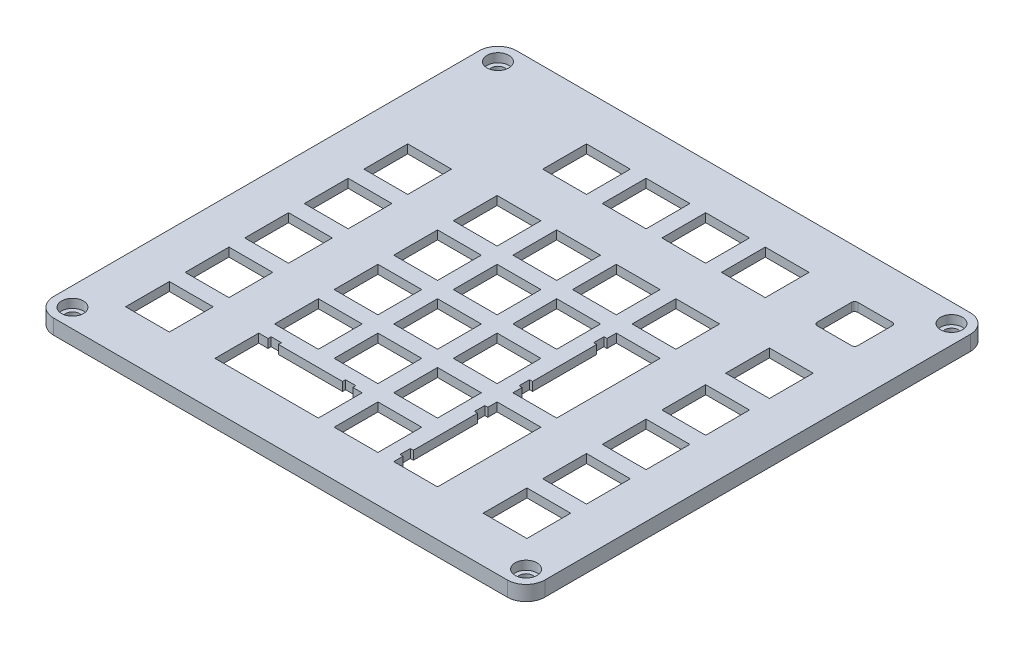
SolidWorks part; units mm, degrees
material "ABS PC"
ref_plane "Front" through (0, 0, 0) normal (0, 0, 1) x (1, 0, 0)
ref_plane "Top" through (0, 0, 0) normal (0, 1, 0) x (1, 0, 0)
ref_plane "Right" through (0, 0, 0) normal (1, 0, 0) x (0, 0, -1)
other "Bounding Box"
ref_plane "Default Plane" through (-37.2876, 0, 53.2522) normal (-0.1736, 0, -0.9848) x (-0.9848, 0, 0.1736)
sketch "Sketch1" plane through (0, 0, 0) normal (0, 1, 0) x (1, 0, 0)
  line L0 (78.5946, 148.4241) -> (78.5951, 0.4241) construction
  line L1 (0.0951, 74.4246) -> (157.0951, 74.4241) construction
  line L2 (76.0691, 29.038) -> (43.0195, 15.0385) construction
  line L3 (43.0195, 29.038) -> (76.0691, 15.0385) construction
  line L4 (135.7441, 106.5548) -> (135.7441, 137.3637) construction
  line L5 (114.1691, 126.8136) -> (153.3059, 126.8136) construction
  line L7 (129.2441, 133.3136) -> (142.2441, 133.3136)
  line L8 (129.2441, 133.3136) -> (129.2441, 120.3136)
  line L9 (129.2441, 120.3136) -> (142.2441, 120.3136)
  line L10 (142.2441, 133.3136) -> (142.2441, 120.3136)
  line L11 (129.2441, 133.3136) -> (142.2441, 120.3136) construction
  line L12 (129.2441, 120.3136) -> (142.2441, 133.3136) construction
  line L20 (157.0951, 142.4241) -> (157.0951, 6.4241)
  line L41 (151.0951, 0.4241) -> (6.0951, 0.4241)
  line L62 (0.0951, 6.424) -> (0.0951, 142.4251)
  line L83 (6.0941, 148.4241) -> (151.0951, 148.4241)
  line L84 (76.0691, 15.0385) -> (76.0691, 29.038)
  line L85 (76.0691, 29.038) -> (73.0938, 29.038)
  line L86 (73.0938, 29.038) -> (73.0938, 30.0081)
  line L87 (73.0938, 30.0081) -> (69.795, 30.0081)
  line L88 (69.795, 30.0081) -> (69.795, 29.038)
  line L89 (69.795, 29.038) -> (49.2936, 29.038)
  line L90 (49.2936, 29.038) -> (49.2936, 30.0081)
  line L91 (49.2936, 30.0081) -> (45.9948, 30.0081)
  line L92 (45.9948, 30.0081) -> (45.9948, 29.038)
  line L93 (45.9948, 29.038) -> (43.0195, 29.038)
  line L94 (43.0195, 29.038) -> (43.0195, 15.0385)
  line L95 (43.0195, 15.0385) -> (76.0691, 15.0385)
  line L96 (128.7441, 29.038) -> (142.7441, 29.038)
  line L97 (142.7441, 29.038) -> (142.7441, 15.0385)
  line L98 (142.7441, 15.0385) -> (128.7441, 15.0385)
  line L99 (128.7441, 15.0385) -> (128.7441, 29.038)
  line L100 (100.1691, 48.0882) -> (100.1691, 45.1129)
  line L101 (100.1691, 45.1129) -> (99.1995, 45.1129)
  line L102 (99.1995, 45.1129) -> (99.1995, 41.8123)
  line L103 (99.1995, 41.8123) -> (100.1691, 41.8123)
  line L104 (100.1691, 41.8123) -> (100.1691, 21.3128)
  line L105 (100.1691, 21.3128) -> (99.1995, 21.3128)
  line L106 (99.1995, 21.3128) -> (99.1995, 18.0123)
  line L107 (99.1995, 18.0123) -> (100.1691, 18.0123)
  line L108 (100.1691, 18.0123) -> (100.1691, 15.0385)
  line L109 (100.1691, 15.0385) -> (114.1691, 15.0385)
  line L110 (114.1691, 15.0385) -> (114.1691, 48.0882)
  line L111 (114.1691, 48.0882) -> (100.1691, 48.0882)
  line L112 (81.1195, 29.038) -> (95.1192, 29.038)
  line L113 (95.1192, 29.038) -> (95.1192, 15.0385)
  line L114 (95.1192, 15.0385) -> (81.1195, 15.0385)
  line L115 (81.1195, 15.0385) -> (81.1195, 29.038)
  line L116 (14.4432, 29.038) -> (28.4441, 29.038)
  line L117 (28.4441, 29.038) -> (28.4441, 15.0385)
  line L118 (28.4441, 15.0385) -> (14.4432, 15.0385)
  line L119 (14.4432, 15.0385) -> (14.4432, 29.038)
  line L120 (128.7441, 48.0882) -> (142.7441, 48.0882)
  line L121 (142.7441, 48.0882) -> (142.7441, 34.0885)
  line L122 (142.7441, 34.0885) -> (128.7441, 34.0885)
  line L123 (128.7441, 34.0885) -> (128.7441, 48.0882)
  line L124 (81.1195, 48.0882) -> (95.1192, 48.0882)
  line L125 (95.1192, 48.0882) -> (95.1192, 34.0885)
  line L126 (95.1192, 34.0885) -> (81.1195, 34.0885)
  line L127 (81.1195, 34.0885) -> (81.1195, 48.0882)
  line L128 (62.0695, 48.0882) -> (76.0691, 48.0882)
  line L129 (76.0691, 48.0882) -> (76.0691, 34.0885)
  line L130 (76.0691, 34.0885) -> (62.0695, 34.0885)
  line L131 (62.0695, 34.0885) -> (62.0695, 48.0882)
  line L132 (43.0195, 48.0882) -> (57.0191, 48.0882)
  line L133 (57.0191, 48.0882) -> (57.0191, 34.0885)
  line L134 (57.0191, 34.0885) -> (43.0195, 34.0885)
  line L135 (43.0195, 34.0885) -> (43.0195, 48.0882)
  line L136 (14.4432, 48.0882) -> (28.4441, 48.0882)
  line L137 (28.4441, 48.0882) -> (28.4441, 34.0885)
  line L138 (28.4441, 34.0885) -> (14.4432, 34.0885)
  line L139 (14.4432, 34.0885) -> (14.4432, 48.0882)
  line L140 (128.7441, 67.1382) -> (142.7441, 67.1382)
  line L141 (142.7441, 67.1382) -> (142.7441, 53.1386)
  line L142 (142.7441, 53.1386) -> (128.7441, 53.1386)
  line L143 (128.7441, 53.1386) -> (128.7441, 67.1382)
  line L144 (100.1691, 86.1882) -> (100.1691, 83.2129)
  line L145 (100.1691, 83.2129) -> (99.1995, 83.2129)
  line L146 (99.1995, 83.2129) -> (99.1995, 79.9123)
  line L147 (99.1995, 79.9123) -> (100.1691, 79.9123)
  line L148 (100.1691, 79.9123) -> (100.1691, 59.4127)
  line L149 (100.1691, 59.4127) -> (99.1995, 59.4127)
  line L150 (99.1995, 59.4127) -> (99.1995, 56.1125)
  line L151 (99.1995, 56.1125) -> (100.1691, 56.1125)
  line L152 (100.1691, 56.1125) -> (100.1691, 53.1386)
  line L153 (100.1691, 53.1386) -> (114.1691, 53.1386)
  line L154 (114.1691, 53.1386) -> (114.1691, 86.1882)
  line L155 (114.1691, 86.1882) -> (100.1691, 86.1882)
  line L156 (81.1195, 67.1382) -> (95.1192, 67.1382)
  line L157 (95.1192, 67.1382) -> (95.1192, 53.1386)
  line L158 (95.1192, 53.1386) -> (81.1195, 53.1386)
  line L159 (81.1195, 53.1386) -> (81.1195, 67.1382)
  line L160 (62.0695, 67.1382) -> (76.0691, 67.1382)
  line L161 (76.0691, 67.1382) -> (76.0691, 53.1386)
  line L162 (76.0691, 53.1386) -> (62.0695, 53.1386)
  line L163 (62.0695, 53.1386) -> (62.0695, 67.1382)
  line L164 (43.0195, 67.1382) -> (57.0191, 67.1382)
  line L165 (57.0191, 67.1382) -> (57.0191, 53.1386)
  line L166 (57.0191, 53.1386) -> (43.0195, 53.1386)
  line L167 (43.0195, 53.1386) -> (43.0195, 67.1382)
  line L168 (14.4432, 67.1382) -> (28.4441, 67.1382)
  line L169 (28.4441, 67.1382) -> (28.4441, 53.1386)
  line L170 (28.4441, 53.1386) -> (14.4432, 53.1386)
  line L171 (14.4432, 53.1386) -> (14.4432, 67.1382)
  line L172 (128.7441, 86.1882) -> (142.7441, 86.1882)
  line L173 (142.7441, 86.1882) -> (142.7441, 72.1886)
  line L174 (142.7441, 72.1886) -> (128.7441, 72.1886)
  line L175 (128.7441, 72.1886) -> (128.7441, 86.1882)
  line L176 (81.1195, 86.1882) -> (95.1192, 86.1882)
  line L177 (95.1192, 86.1882) -> (95.1192, 72.1886)
  line L178 (95.1192, 72.1886) -> (81.1195, 72.1886)
  line L179 (81.1195, 72.1886) -> (81.1195, 86.1882)
  line L180 (62.0695, 86.1882) -> (76.0691, 86.1882)
  line L181 (76.0691, 86.1882) -> (76.0691, 72.1886)
  line L182 (76.0691, 72.1886) -> (62.0695, 72.1886)
  line L183 (62.0695, 72.1886) -> (62.0695, 86.1882)
  line L184 (43.0195, 86.1882) -> (57.0191, 86.1882)
  line L185 (57.0191, 86.1882) -> (57.0191, 72.1886)
  line L186 (57.0191, 72.1886) -> (43.0195, 72.1886)
  line L187 (43.0195, 72.1886) -> (43.0195, 86.1882)
  line L188 (14.4432, 86.1882) -> (28.4441, 86.1882)
  line L189 (28.4441, 86.1882) -> (28.4441, 72.1886)
  line L190 (28.4441, 72.1886) -> (14.4432, 72.1886)
  line L191 (14.4432, 72.1886) -> (14.4432, 86.1882)
  line L192 (128.7441, 106.5548) -> (142.7441, 106.5548)
  line L193 (142.7441, 106.5548) -> (142.7441, 92.5554)
  line L194 (142.7441, 92.5554) -> (128.7441, 92.5554)
  line L195 (128.7441, 92.5554) -> (128.7441, 106.5548)
  line L196 (100.1691, 105.2381) -> (114.1691, 105.2381)
  line L197 (114.1691, 105.2381) -> (114.1691, 91.2386)
  line L198 (114.1691, 91.2386) -> (100.1691, 91.2386)
  line L199 (100.1691, 91.2386) -> (100.1691, 105.2381)
  line L200 (81.1195, 105.2381) -> (95.1192, 105.2381)
  line L201 (95.1192, 105.2381) -> (95.1192, 91.2386)
  line L202 (95.1192, 91.2386) -> (81.1195, 91.2386)
  line L203 (81.1195, 91.2386) -> (81.1195, 105.2381)
  line L204 (62.0695, 105.2381) -> (76.0691, 105.2381)
  line L205 (76.0691, 105.2381) -> (76.0691, 91.2386)
  line L206 (76.0691, 91.2386) -> (62.0695, 91.2386)
  line L207 (62.0695, 91.2386) -> (62.0695, 105.2381)
  line L208 (43.0195, 105.2381) -> (57.0191, 105.2381)
  line L209 (57.0191, 105.2381) -> (57.0191, 91.2386)
  line L210 (57.0191, 91.2386) -> (43.0195, 91.2386)
  line L211 (43.0195, 91.2386) -> (43.0195, 105.2381)
  line L212 (14.4432, 105.2381) -> (28.4441, 105.2381)
  line L213 (28.4441, 105.2381) -> (28.4441, 91.2386)
  line L214 (28.4441, 91.2386) -> (14.4432, 91.2386)
  line L215 (14.4432, 91.2386) -> (14.4432, 105.2381)
  line L216 (100.1691, 133.8131) -> (114.1691, 133.8131)
  line L217 (114.1691, 133.8131) -> (114.1691, 119.8141)
  line L218 (114.1691, 119.8141) -> (100.1691, 119.8141)
  line L219 (100.1691, 119.8141) -> (100.1691, 133.8131)
  line L220 (81.1195, 133.8131) -> (95.1192, 133.8131)
  line L221 (95.1192, 133.8131) -> (95.1192, 119.8141)
  line L222 (95.1192, 119.8141) -> (81.1195, 119.8141)
  line L223 (81.1195, 119.8141) -> (81.1195, 133.8131)
  line L224 (62.0695, 133.8131) -> (76.0691, 133.8131)
  line L225 (76.0691, 133.8131) -> (76.0691, 119.8141)
  line L226 (76.0691, 119.8141) -> (62.0695, 119.8141)
  line L227 (62.0695, 119.8141) -> (62.0695, 133.8131)
  line L228 (43.0195, 133.8131) -> (57.0191, 133.8131)
  line L229 (57.0191, 133.8131) -> (57.0191, 119.8141)
  line L230 (57.0191, 119.8141) -> (43.0195, 119.8141)
  line L231 (43.0195, 119.8141) -> (43.0195, 133.8131)
  arc A0 (151.0951, 0.4241) -> (157.0951, 6.4241) centre (151.0951, 6.4241) ccw
  arc A1 (6.0951, 0.4241) -> (0.0951, 6.424) centre (6.0951, 6.424) cw
  arc A2 (0.0951, 142.4251) -> (6.0941, 148.4241) centre (6.0941, 142.4251) cw
  arc A3 (151.0951, 148.4241) -> (157.0951, 142.4241) centre (151.0951, 142.4241) cw
  circle A4 centre (6.0951, 142.4241) radius 2.15
  circle A5 centre (151.0941, 142.4246) radius 2.15
  circle A6 centre (151.0937, 6.4236) radius 2.15
  circle A7 centre (6.0947, 6.425) radius 2.15
  point P11 (151.0951, 142.4255)
  point P22 (135.7441, 126.8136)
  point P25 (135.7441, 126.8136)
  point P30 (140.204, 123.9216)
  dimension "D1" = 157
  dimension "D3" = 6
  dimension "D5" = 4.3
  dimension "D2" = 148
  dimension "D4" = 6
  dimension "D6" = 13
  dimension "D7" = 13
extrude "Boss-Extrude1" add sketch "Sketch1" along normal blind 4.78
sketch "Sketch2" plane through (0, 0, 0) normal (0, -1, 0) x (1, 0, 0)
  line L0 (9.0951, -9.4241) -> (9.0951, -139.4241)
  line L1 (9.0951, -139.4241) -> (148.0951, -139.4241)
  line L2 (148.0951, -139.4241) -> (148.0951, -9.4241)
  line L3 (148.0951, -9.4241) -> (9.0951, -9.4241)
  line L4 (157.0951, -142.4241) -> (157.0951, -6.4241)
  line L5 (151.0951, -0.4241) -> (6.0951, -0.4241)
  line L6 (0.0951, -6.424) -> (0.0951, -142.4251)
  line L7 (6.0941, -148.4241) -> (151.0951, -148.4241)
  line L8 (157.0951, -142.4241) -> (157.0951, -6.4241)
  line L9 (151.0951, -0.4241) -> (6.0951, -0.4241)
  line L10 (0.0951, -6.424) -> (0.0951, -142.4251)
  line L11 (6.0941, -148.4241) -> (151.0951, -148.4241)
  arc A0 (9.0951, -139.4241) -> (9.0951, -139.4241) centre (9.0951, -139.4241) ccw
  arc A1 (148.0951, -139.4241) -> (148.0951, -139.4241) centre (148.0951, -139.4241) ccw
  arc A2 (148.0951, -9.4241) -> (148.0951, -9.4241) centre (148.0951, -9.4241) ccw
  arc A3 (9.0951, -9.4241) -> (9.0951, -9.4241) centre (9.0951, -9.4241) ccw
  arc A4 (151.0951, -148.4241) -> (157.0951, -142.4241) centre (151.0951, -142.4241) ccw
  arc A5 (157.0951, -6.4241) -> (151.0951, -0.4241) centre (151.0951, -6.4241) ccw
  arc A6 (6.0951, -0.4241) -> (0.0951, -6.424) centre (6.0951, -6.424) ccw
  arc A7 (0.0951, -142.4251) -> (6.0941, -148.4241) centre (6.0941, -142.4251) ccw
  arc A8 (151.0951, -148.4241) -> (157.0951, -142.4241) centre (151.0951, -142.4241) ccw
  arc A9 (157.0951, -6.4241) -> (151.0951, -0.4241) centre (151.0951, -6.4241) ccw
  arc A10 (6.0951, -0.4241) -> (0.0951, -6.424) centre (6.0951, -6.424) ccw
  arc A11 (0.0951, -142.4251) -> (6.0941, -148.4241) centre (6.0941, -142.4251) ccw
  dimension "D1" = 0
  dimension "D2" = 9
extrude "Cut-Extrude1" cut sketch "Sketch2" against normal blind 2 contours L2 L3 L0 L1 region at (78.5951, 0, -74.4241)
sketch "Sketch4" plane through (0, 0, 0) normal (0, -1, 0) x (1, 0, 0)
  line L0 (144.0951, -139.4241) -> (144.0951, -145.4241)
  line L1 (9.0951, -139.4241) -> (148.0951, -139.4241) construction
  line L2 (144.0951, -145.4241) -> (124.0951, -145.4241)
  line L3 (124.0951, -145.4241) -> (124.0951, -139.4241)
  line L4 (124.0951, -139.4241) -> (144.0951, -139.4241)
  line L5 (151.0951, -148.4241) -> (6.0941, -148.4241) construction
  line L6 (148.0951, -139.4241) -> (148.0951, -9.4241) construction
  dimension "D1" = 3
  dimension "D2" = 4
  dimension "D3" = 20
extrude "Cut-Extrude2" cut sketch "Sketch4" against normal blind 2
sketch "Sketch5" plane through (0, 0, 0) normal (0, -1, 0) x (1, 0, 0)
  line L0 (15.0951, -146.4241) -> (15.0951, -139.4241)
  line L2 (9.0951, -139.4241) -> (124.0951, -139.4241) construction
  line L3 (15.0951, -139.4241) -> (35.0951, -139.4241)
  line L4 (9.0951, -139.4241) -> (124.0951, -139.4241) construction
  line L5 (35.0951, -139.4241) -> (35.0951, -146.4241)
  line L6 (35.0951, -146.4241) -> (15.0951, -146.4241)
  line L7 (0.0951, -142.4251) -> (0.0951, -6.424) construction
  line L8 (151.0951, -148.4241) -> (6.0941, -148.4241) construction
  point P12 (25.0951, -146.4241)
  dimension "D1" = 25
  dimension "D2" = 20
  dimension "D3" = 2
extrude "Cut-Extrude3" cut sketch "Sketch5" against normal blind 2
sketch "Sketch6" plane through (0, 4.78, 0) normal (0, 1, 0) x (1, 0, 0)
  circle A0 centre (6.0951, 142.4241) radius 3.5
  circle A1 centre (151.0941, 142.4246) radius 3.5
  circle A2 centre (151.0937, 6.4236) radius 3.5
  circle A3 centre (6.0947, 6.425) radius 3.5
  dimension "D1" = 7
extrude "Cut-Extrude4" cut sketch "Sketch6" against normal blind 2.8
fillet "Fillet1" radius 1 4 edges at (142.2441, 3.39, -120.3136) (129.2441, 3.39, -120.3136) (142.2441, 3.39, -133.3136) (129.2441, 3.39, -133.3136)
